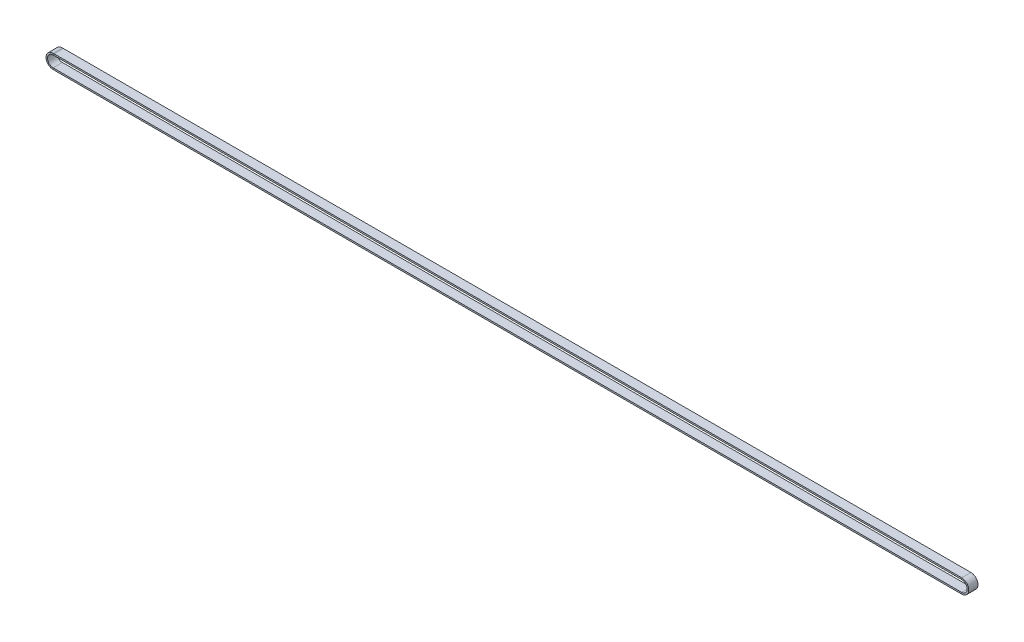
SolidWorks part; units mm, degrees
ref_plane "Front Plane" through (0, 0, 0) normal (0, 0, 1) x (1, 0, 0)
ref_plane "Top Plane" through (0, 0, 0) normal (0, 1, 0) x (1, 0, 0)
ref_plane "Right Plane" through (0, 0, 0) normal (1, 0, 0) x (0, 0, -1)
sketch "Sketch2" plane through (0, 0, 0) normal (0, 0, 1) x (1, 0, 0)
  line L0 (0, 0) -> (1, 0) construction
  line L1 (0, 0) -> (0, 1) construction
  line L2 (-1, -15.9274) -> (883.5206, -15.9274)
  line L3 (883.5206, -29.7274) -> (-1, -29.7274)
  arc A0 (-1, -29.7274) -> (-1, -15.9274) centre (-1, -22.8274) cw
  arc A1 (883.5206, -15.9274) -> (883.5206, -29.7274) centre (883.5206, -22.8274) cw
sketch "Sketch3" plane through (0, 0, 0) normal (1, 0, 0) x (0, 0, -1)
  line L1 (0, -17.4274) -> (-9, -17.4274)
  line L2 (0, -17.4274) -> (0, -15.9274)
  line L3 (0, -15.9274) -> (-9, -15.9274)
  line L4 (-9, -17.4274) -> (-9, -15.9274)
  dimension "D1" = 9
  dimension "D2" = 1.5
sweep "Sweep1" add profiles "Sketch3" path "Sketch2"
